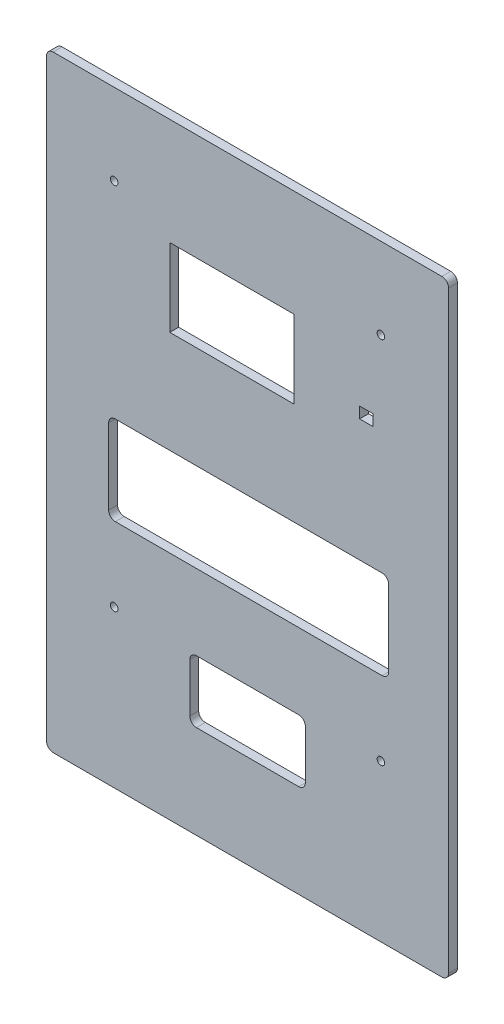
SolidWorks part; units mm, degrees
material "Verre"
ref_plane "Plan de face" through (0, 0, 0) normal (0, 0, 1) x (1, 0, 0)
ref_plane "Plan de dessus" through (0, 0, 0) normal (0, 1, 0) x (1, 0, 0)
ref_plane "Plan de droite" through (0, 0, 0) normal (1, 0, 0) x (0, 0, -1)
sketch "Esquisse1" plane through (0, 0, 0) normal (0, 0, 1) x (1, 0, 0)
  line L1 (0, 0) -> (180.86, 0)
  line L2 (0, 0) -> (0, 273)
  line L3 (0, 273) -> (180.86, 273)
  line L4 (180.86, 0) -> (180.86, 273)
  line L5 (64.43, 70) -> (116.43, 70)
  line L6 (64.43, 70) -> (64.43, 42)
  line L7 (64.43, 42) -> (116.43, 42)
  line L8 (116.43, 70) -> (116.43, 42)
  line L9 (27.93, 144) -> (153.93, 144)
  line L10 (27.93, 144) -> (27.93, 104)
  line L11 (27.93, 104) -> (153.93, 104)
  line L12 (153.93, 144) -> (153.93, 104)
  line L13 (55.43, 225) -> (111.43, 225)
  line L14 (55.43, 225) -> (55.43, 190)
  line L15 (55.43, 190) -> (111.43, 190)
  line L16 (111.43, 225) -> (111.43, 190)
  line L17 (140.86, 204) -> (146.86, 204)
  line L18 (140.86, 204) -> (140.86, 199)
  line L19 (140.86, 199) -> (146.86, 199)
  line L20 (146.86, 204) -> (146.86, 199)
  circle A0 centre (30.43, 236.5) radius 1.5
  circle A1 centre (150.43, 236.5) radius 1.5
  circle A2 centre (30.43, 70.5) radius 1.5
  circle A3 centre (150.43, 70.5) radius 1.5
  dimension "D5" = 3
  dimension "D8" = 3
  dimension "D13" = 3
  dimension "D14" = 3
  dimension "D1" = 180.86
  dimension "D2" = 273
  dimension "D3" = 30.43
  dimension "D4" = 36.5
  dimension "D6" = 36.5
  dimension "D7" = 30.43
  dimension "D9" = 30.43
  dimension "D10" = 30.43
  dimension "D11" = 70.5
  dimension "D12" = 70.5
  dimension "D15" = 64.43
  dimension "D16" = 42
  dimension "D17" = 28
  dimension "D18" = 34
  dimension "D19" = 40
  dimension "D20" = 52
  dimension "D21" = 27.93
  dimension "D22" = 26.93
  dimension "D23" = 48
  dimension "D24" = 35
  dimension "D25" = 55.43
  dimension "D26" = 56
  dimension "D27" = 6
  dimension "D28" = 5
  dimension "D29" = 40
  dimension "D30" = 74
extrude "Boss.-Extru.1" add sketch "Esquisse1" along normal blind 4
hole_wizard "Dégagement M31" positions "Esquisse2" profile "Esquisse3" hole size "M3" standard "ISO" end condition through all
sketch "Esquisse2" plane through (0, 0, 4) normal (0, 0, 1) x (1, 0, 0)
  point P0 (30.43, 236.5)
  point P3 (150.43, 236.5)
  point P6 (150.43, 70.5)
  point P9 (30.43, 70.5)
sketch "Esquisse3" plane through (30.43, 236.5, 4) normal (1, 0, 0) x (0, -1, 0)
  line L0 (0, 0) -> (0, 4)
  line L1 (0, 4) -> (1.7, 4)
  line L2 (1.7, 4) -> (1.7, 0)
  line L5 (1.7, 0) -> (0, 0)
  line L11 (0, -6.35) -> (0, 107.95) construction
  dimension "Diamètre du perçage jusqu'au prochain" = 3.4
  dimension "Profondeur du perçage jusqu'au prochain" = 4
fillet "Congé1" radius 3 12 edges at (0, 0, 2) (180.86, 0, 2) (116.43, 42, 2) (64.43, 42, 2) (116.43, 70, 2) (64.43, 70, 2) (153.93, 104, 2) (27.93, 104, 2) (153.93, 144, 2) (27.93, 144, 2) (180.86, 273, 2) (0, 273, 2)
equation "\"D7@Esquisse1\"=\"D3@Esquisse1\""
equation "\"D9@Esquisse1\"=\"D3@Esquisse1\""
equation "\"D10@Esquisse1\"=\"D3@Esquisse1\""
equation "\"D12@Esquisse1\"=\"D11@Esquisse1\""
equation "\"D13@Esquisse1\"=\"D5@Esquisse1\""
equation "\"D14@Esquisse1\"=\"D8@Esquisse1\""
